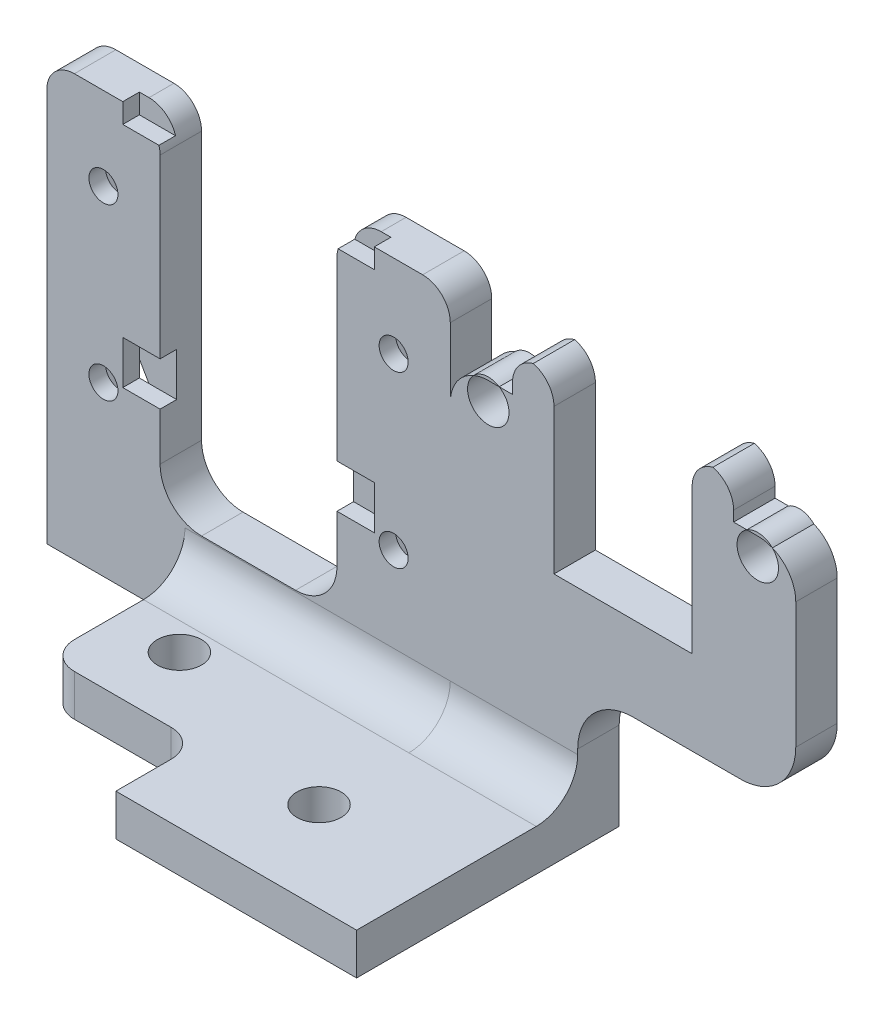
SolidWorks part; units mm, degrees
ref_plane "Plano frontal" through (0, 0, 0) normal (0, 0, 1) x (1, 0, 0)
ref_plane "Plano superior" through (0, 0, 0) normal (0, 1, 0) x (1, 0, 0)
ref_plane "Plano direito" through (0, 0, 0) normal (1, 0, 0) x (0, 0, -1)
other "Centro da massa"
sketch "Esboço2" plane through (0, 0, -1) normal (0, 0, -1) x (-1, 0, 0)
  line L1 (14.6, 8.1) -> (6.4, 8.1)
  line L2 (14.6, 8.1) -> (14.6, -22.3604)
  line L3 (14.6, -22.3604) -> (6.4, -22.3604)
  line L4 (6.4, 8.1) -> (6.4, -22.3604)
  line L5 (6.4, 8.1) -> (-21.6025, 8.1) construction
  line L6 (-12.6, -12) -> (-12.6, 12) construction
  line L7 (-14.6, 8.1) -> (-6.4, 8.1)
  line L8 (-14.6, 8.1) -> (-14.6, -22.3604)
  line L9 (-14.6, -22.3604) -> (-6.4, -22.3604)
  line L10 (-6.4, 8.1) -> (-6.4, -22.3604)
  line L11 (12.6, -12) -> (12.6, 12) construction
  line L12 (-4.4, -2.7) -> (-4.4, 6.1) construction
  circle A0 centre (-10.5, 2.1) radius 1.05 construction
  dimension "D3" = 6
  dimension "D1" = 2
  dimension "D2" = 2
  dimension "D4" = 2
extrude "Ressalto-extrusão1" add sketch "Esboço2" along normal blind 3
sketch "Esboço3" plane through (-6.4, 0, 0) normal (1, 0, 0) x (0, 0, -1)
  line L0 (4, 8.1) -> (4, -22.3604) construction
  line L1 (1, -22.3604) -> (4, -22.3604)
  line L2 (1, -22.3604) -> (1, -16.2722)
  line L3 (1, -16.2722) -> (4, -16.2722)
  line L4 (4, -22.3604) -> (4, -16.2722)
extrude "Ressalto-extrusão2" add sketch "Esboço3" along normal up to next
sketch "Esboço4" plane through (0, 0, -1) normal (0, 0, 1) x (1, 0, 0)
  line L0 (14.6, -22.3604) -> (-14.6, -22.3604) construction
  line L1 (-6.4, -22.3604) -> (6.4, -22.3604)
  line L2 (-6.4, -22.3604) -> (-6.4, -19.3604)
  line L3 (-6.4, -19.3604) -> (6.4, -19.3604)
  line L4 (6.4, -22.3604) -> (6.4, -19.3604)
  line L5 (6.4, -16.2722) -> (6.4, 8.1) construction
  line L6 (-6.4, 8.1) -> (-6.4, -16.2722) construction
  dimension "D1" = 3
extrude "Ressalto-extrusão3" add sketch "Esboço4" along normal blind 10
sketch "Esboço5" plane through (0, 0, -1) normal (0, 0, 1) x (1, 0, 0)
  line L0 (14.6, 8.1) -> (14.6, -22.3604) construction
  line L1 (-14.6, -22.3604) -> (-6.4, -22.3604)
  line L2 (-14.6, -22.3604) -> (-14.6, -19.3604)
  line L3 (-14.6, -19.3604) -> (-6.4, -19.3604)
  line L4 (-6.4, -22.3604) -> (-6.4, -19.3604)
  line L5 (6.4, -22.3604) -> (14.6, -22.3604)
  line L6 (6.4, -22.3604) -> (6.4, -19.3604)
  line L7 (6.4, -19.3604) -> (14.6, -19.3604)
  line L8 (14.6, -22.3604) -> (14.6, -19.3604)
  line L9 (-6.4, -19.3604) -> (-6.4, -22.3604) construction
  dimension "D1" = 3
extrude "Ressalto-extrusão4" add sketch "Esboço5" along normal blind 16
sketch "Esboço6" plane through (0, -19.3604, 0) normal (0, 1, 0) x (1, 0, 0)
  line L0 (6.4, -9) -> (-6.4, 1) construction
  line L1 (6.4, -15) -> (6.4, -9) construction
  line L2 (-14.6, -10.5) -> (-6.4, -10.5) construction
  line L3 (-14.6, -15) -> (-14.6, 1) construction
  line L4 (-6.4, -15) -> (-6.4, -9) construction
  line L5 (-6.4, -10.5) -> (6.4, -10.5) construction
  line L6 (6.4, -10.5) -> (14.6, -10.5) construction
  line L7 (14.6, -15) -> (14.6, 1) construction
  line L8 (14.6, -15) -> (6.4, -15) construction
  circle A0 centre (0, -4) radius 1.6
  circle A1 centre (10.5, -10.5) radius 1.6
  circle A2 centre (-10.5, -10.5) radius 1.6
  dimension "D1" = 3.2
  dimension "D2" = 4.5
sketch "Esboço8" plane through (0, 0, -1) normal (0, 0, 1) x (1, 0, 0)
  circle A0 centre (-10.5, 2.1) radius 1.05
  circle A1 centre (10.5, 2.1) radius 1.05
  circle A2 centre (10.5, -10.2) radius 1.05
  circle A3 centre (-10.5, -10.2) radius 1.05
  dimension "D1" = 2.1
extrude "Corte-extrusão3" cut sketch "Esboço8" against normal through all
fillet "Filete1" radius 3 2 edges at (6.4, -16.2722, -2.5) (-6.4, -16.2722, -2.5)
sketch "Esboço9" plane through (6.4, 0, 0) normal (-1, 0, 0) x (0, 0, 1)
  line L0 (-1, -13.2722) -> (-1, 8.1) construction
  line L1 (-1, -6.6712) -> (-2.2, -6.6712)
  line L2 (-1, -6.6712) -> (-1, -9.82)
  line L3 (-1, -9.82) -> (-2.2, -9.82)
  line L4 (-2.2, -6.6712) -> (-2.2, -9.82)
extrude "Corte-extrusão4" cut sketch "Esboço9" against normal blind 2.7
fillet "Filete2" radius 3 1 edges at (0, -19.3604, -1)
sketch "Esboço10" plane through (0, 0, -4) normal (0, 0, -1) x (-1, 0, 0)
  line L0 (0, -16.2722) -> (0, 4.5459) construction
  line L1 (12.8094, 2.1) -> (11.6547, 4.1)
  line L2 (11.6547, 4.1) -> (9.3453, 4.1)
  line L3 (9.3453, 4.1) -> (8.1906, 2.1)
  line L4 (8.1906, 2.1) -> (9.3453, 0.1)
  line L5 (9.3453, 0.1) -> (11.6547, 0.1)
  line L6 (11.6547, 0.1) -> (12.8094, 2.1)
  line L7 (12.8094, -10.2) -> (11.6547, -8.2)
  line L8 (11.6547, -8.2) -> (9.3453, -8.2)
  line L9 (9.3453, -8.2) -> (8.1906, -10.2)
  line L10 (8.1906, -10.2) -> (9.3453, -12.2)
  line L11 (9.3453, -12.2) -> (11.6547, -12.2)
  line L12 (11.6547, -12.2) -> (12.8094, -10.2)
  line L13 (-3.4, -16.2722) -> (3.4, -16.2722) construction
  line L14 (-11.6547, -12.2) -> (-12.8094, -10.2)
  line L15 (-9.3453, -12.2) -> (-11.6547, -12.2)
  line L16 (-8.1906, -10.2) -> (-9.3453, -12.2)
  line L17 (-9.3453, -8.2) -> (-8.1906, -10.2)
  line L18 (-11.6547, -8.2) -> (-9.3453, -8.2)
  line L19 (-12.8094, -10.2) -> (-11.6547, -8.2)
  line L20 (-11.6547, 0.1) -> (-12.8094, 2.1)
  line L21 (-9.3453, 0.1) -> (-11.6547, 0.1)
  line L22 (-8.1906, 2.1) -> (-9.3453, 0.1)
  line L23 (-9.3453, 4.1) -> (-8.1906, 2.1)
  line L24 (-11.6547, 4.1) -> (-9.3453, 4.1)
  line L25 (-12.8094, 2.1) -> (-11.6547, 4.1)
  circle A0 centre (10.5, 2.1) radius 2 construction
  circle A1 centre (10.5, -10.2) radius 2 construction
  circle A2 centre (-10.5, -10.2) radius 2 construction
  circle A3 centre (-10.5, 2.1) radius 2 construction
  point P25 (10.5, 0.1)
  dimension "D1" = 4
extrude "Corte-extrusão5" cut sketch "Esboço10" against normal blind 1.8
sketch "Esboço11" plane through (0, -19.3604, 0) normal (0, 1, 0) x (1, 0, 0)
  line L0 (0, 0) -> (0, -34) construction
  line L1 (8.25, -11) -> (-8.25, -11)
  line L2 (8.25, -11) -> (8.25, -17)
  line L3 (8.25, -17) -> (-8.25, -17)
  line L4 (-8.25, -11) -> (-8.25, -17)
  line L5 (6.4, -9) -> (-6.4, -9) construction
  point P7 (0, -17)
  dimension "D1" = 16.5
  dimension "D2" = 6
  dimension "D3" = 2
sketch "Esboço13" plane through (0, 0, -1) normal (0, 0, 1) x (1, 0, 0)
  line L0 (12.6426, 0) -> (0, 0) construction
  line L1 (12.6426, 12) -> (12.6426, -12) construction
  line L2 (9.1, -6.6712) -> (6.4, -6.6712) construction
  line L3 (6.4, -6.6712) -> (6.4, -9.82) construction
  line L4 (9.1, -9.82) -> (6.4, -9.82) construction
  line L5 (9.1, -9.82) -> (9.1, -6.6712) construction
  line L6 (9.1, -6.6712) -> (6.4, -6.6712)
  line L7 (6.4, -6.6712) -> (6.4, -9.82)
  line L8 (9.1, -9.82) -> (6.4, -9.82)
  line L9 (9.1, -9.82) -> (9.1, -6.6712)
  line L10 (0, 0) -> (0, -9.82) construction
  line L11 (9.1, 9.82) -> (9.1, 6.6712)
  line L12 (9.1, 9.82) -> (6.4, 9.82)
  line L13 (6.4, 6.6712) -> (6.4, 9.82)
  line L14 (9.1, 6.6712) -> (6.4, 6.6712)
  line L15 (-9.1, 6.6712) -> (-6.4, 6.6712)
  line L16 (-6.4, 6.6712) -> (-6.4, 9.82)
  line L17 (-9.1, 9.82) -> (-6.4, 9.82)
  line L18 (-9.1, 9.82) -> (-9.1, 6.6712)
  line L19 (-9.1, -9.82) -> (-9.1, -6.6712)
  line L20 (-9.1, -9.82) -> (-6.4, -9.82)
  line L21 (-6.4, -6.6712) -> (-6.4, -9.82)
  line L22 (-9.1, -6.6712) -> (-6.4, -6.6712)
extrude "Corte-extrusão7" cut sketch "Esboço13" against normal up to surface (1.2 mm away) up to face at (7.882, -8.3215, -2.2)
sketch "Esboço14" plane through (14.6, 0, 0) normal (1, 0, 0) x (0, 0, -1)
  line L0 (-15, -19.3604) -> (4, -19.3604)
  line L1 (4, 8.1) -> (4, -22.3604) construction
  line L2 (4, -19.3604) -> (4, -22.3604)
  line L3 (4, -22.3604) -> (-15, -22.3604)
  line L4 (-15, -22.3604) -> (-15, -19.3604)
extrude "Ressalto-extrusão5" add sketch "Esboço14" along normal blind 25
sketch "Esboço15" plane through (0, -19.3604, 0) normal (0, 1, 0) x (1, 0, 0)
  line L0 (14.6, 1) -> (39.6, 1)
  line L1 (39.6, 4) -> (39.6, -15) construction
  line L2 (39.6, 1) -> (39.6, 4)
  line L3 (39.6, 4) -> (14.6, 4)
  line L4 (14.6, 4) -> (14.6, 1)
  dimension "D1" = 3
extrude "Ressalto-extrusão6" add sketch "Esboço15" along normal blind 25.96
sketch "Esboço16" plane through (0, 0, -4) normal (0, 0, -1) x (-1, 0, 0)
  line L0 (-14.6, 8.1) -> (-14.6, -16.6485) construction
  line L1 (-39.6, 1.0996) -> (-14.6, 1.0996) construction
  line L2 (-39.6, -22.3604) -> (-39.6, 6.5996) construction
  line L3 (-39.6, 6.5996) -> (-14.6, 6.5996) construction
  line L4 (-27.1, 6.5996) -> (-27.1, -12.0071) construction
  line L5 (-35.1, 6.5996) -> (-35.1, 3.8496) construction
  line L6 (-35.1, 3.8496) -> (-36.85, 3.8496)
  line L7 (-36.85, -1.6504) -> (-35.1, -1.6504)
  line L8 (-35.1, -1.6504) -> (-35.1, -7.4004)
  line L9 (-36.85, 3.8496) -> (-36.85, -4.4528) construction
  line L10 (-35.1, 6.5996) -> (-35.1, 3.8496)
  line L11 (-35.1, 6.5996) -> (-32.1, 6.5996)
  line L12 (-32.1, 6.5996) -> (-32.1, -5.9004)
  line L13 (-35.1, -7.4004) -> (-35.1, -10.4004)
  line L14 (-35.1, -10.4004) -> (-27.1, -10.4004)
  line L15 (-32.1, -5.9004) -> (-22.1, -5.9004)
  line L16 (-19.1, -7.4004) -> (-19.1, -10.4004)
  line L17 (-19.1, -1.6504) -> (-19.1, -7.4004)
  line L18 (-17.35, -1.6504) -> (-19.1, -1.6504)
  line L19 (-19.1, 3.8496) -> (-17.35, 3.8496)
  line L20 (-19.1, 6.5996) -> (-19.1, 3.8496)
  line L21 (-19.1, 6.5996) -> (-22.1, 6.5996)
  line L22 (-22.1, 6.5996) -> (-22.1, -5.9004)
  line L23 (-27.1, -10.4004) -> (-19.1, -10.4004)
  line L24 (-32.1, 6.5996) -> (-22.1, 6.5996)
  line L25 (-39.6, -12.0071) -> (-27.1, -12.0071)
  line L27 (-23.82, -19.3604) -> (-39.6, -19.3604)
  line L28 (-39.6, -22.3604) -> (14.6, -22.3604) construction
  line L29 (-14.6, 8.1) -> (-14.6, 1.0996)
  line L30 (-19.1, 6.5996) -> (-14.6, 8.1)
  line L31 (-39.6, -12.0071) -> (-39.6, -19.3604)
  line L32 (-23.82, -19.3604) -> (-23.82, -12.0071)
  line L33 (-23.82, -12.0071) -> (-27.1, -12.0071)
  arc A0 (-36.85, 3.8496) -> (-36.85, -1.6504) centre (-36.85, 1.0996) ccw
  circle A1 centre (-36.85, 2.5741) radius 1.5
  circle A2 centre (-17.35, 2.5741) radius 1.5
  arc A3 (-17.35, 3.8496) -> (-17.35, -1.6504) centre (-17.35, 1.0996) cw
  point P38 (-27.1, -5.9004)
  line M37 (-14.6, 6.5996) -> (-39.6, 6.5996)
  line M38 (-39.6, 6.5996) -> (-39.6, -22.3604)
  dimension "D6" = 1.75
  dimension "D1" = 5.5
  dimension "D2" = 12.5
  dimension "D3" = 2.75
  dimension "D4" = 1.75
  dimension "D5" = 8
  dimension "D7" = 5.75
  dimension "D8" = 3
  dimension "D9" = 3
  dimension "D10" = 3
  dimension "D11" = 15.78
extrude "Corte-extrusão8" cut sketch "Esboço16" against normal blind 26 contours L27 L25 M38 | A1 | A0 L6 L10 M37 M38 | L22 L12 L15 M37 | A2 | L19 A3 L29 L20 M37 region at (37.5517, 5.0166, -4) region at (36.8451, 2.5173, -4) region at (31.71, -15.6837, -4) region at (27.1, 0.3496, -4) region at (16.6483, 5.0166, -4) region at (17.3549, 2.5173, -4)
fillet "Filete4" radius 4 1 edges at (39.6, -12.0071, -2.5)
fillet "Filete5" radius 2 8 edges at (-14.6, 8.1, -2.5) (-6.4, 8.1, -3.1) (6.4, 8.1, -3.1) (14.6, 8.1, -2.5) (19.1, 6.5996, -2.5) (22.1, 6.5996, -2.5) (35.1, 6.5996, -2.5) (32.1, 6.5996, -2.5)
sketch "Esboço18" plane through (-14.6, 0, 0) normal (-1, 0, 0) x (0, 0, 1)
  line L0 (-1, -16.3604) -> (-1, -22.3604)
  line L1 (-4, -22.3604) -> (15, -22.3604) construction
  line L2 (-1, -22.3604) -> (15, -22.3604)
  line L3 (15, -22.3604) -> (15, -19.3604)
  line L4 (15, -19.3604) -> (-1, -16.3604)
extrude "Corte-extrusão10" cut sketch "Esboço18" against normal blind 10
sketch "Esboço19" plane through (39.6, 0, 0) normal (1, 0, 0) x (0, 0, -1)
  line L0 (-15, -17.3604) -> (-15, -22.3604)
  line L1 (-15, -22.3604) -> (4, -22.3604)
  line L2 (4, -22.3604) -> (4, -17.3604)
  line L3 (4, -17.3604) -> (-15, -17.3604)
  dimension "D1" = 5
extrude "Corte-extrusão13" cut sketch "Esboço19" against normal blind 15.78
fillet "Filete7" radius 4 1 edges at (23.82, -12.0071, -2.5)
fillet "Filete8" radius 3 1 edges at (19.21, -19.3604, -1)
sketch "Esboço20" plane through (0, -19.3604, 0) normal (0, 1, 0) x (1, 0, 0)
  line L0 (14.6, -2) -> (14.6, -15) construction
  line L1 (23.82, -15) -> (6.4, -15) construction
  circle A0 centre (14.6, -8.5) radius 1.6
  circle A1 centre (0, -4) radius 1.6
extrude "Corte-extrusão14" cut sketch "Esboço20" against normal blind 12
fillet "Filete9" radius 2 2 edges at (6.4, -20.8604, 9) (-4.6, -20.8604, 9)
